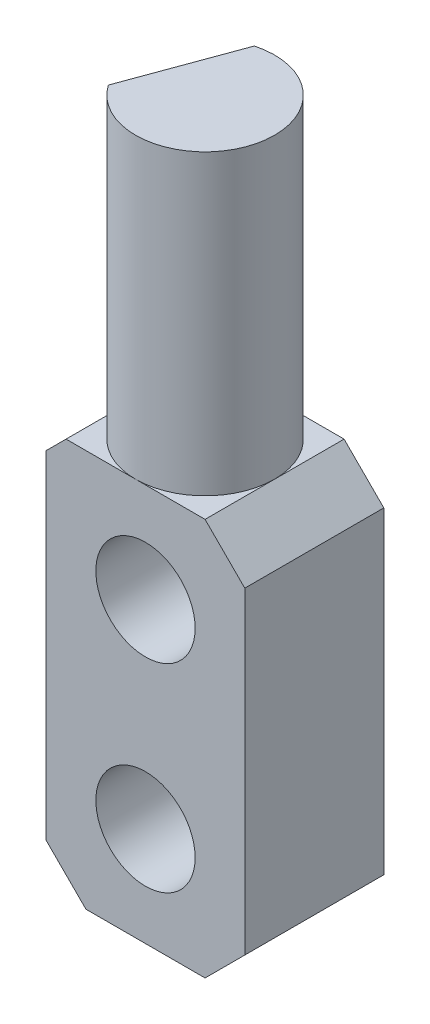
SolidWorks part; units mm, degrees
material "SUS304"
ref_plane "Front" through (0, 0, 0) normal (0, 0, 1) x (1, 0, 0)
ref_plane "Top" through (0, 0, 0) normal (0, 1, 0) x (1, 0, 0)
ref_plane "Right" through (0, 0, 0) normal (1, 0, 0) x (0, 0, -1)
sketch "Sketch1" plane through (0, 0, 0) normal (0, 0, 1) x (1, 0, 0)
  line L1 (0, 0) -> (10, 0)
  line L2 (0, 0) -> (0, 20)
  line L3 (0, 20) -> (10, 20)
  line L4 (10, 0) -> (10, 20)
  dimension "D1" = 20
  dimension "D2" = 10
extrude "Boss-Extrude1" add sketch "Sketch1" along normal blind 7
sketch "Sketch2" plane through (0, 20, 0) normal (0, 1, 0) x (1, 0, 0)
  line L0 (10, 0) -> (0, 0) construction
  line L1 (10, -7) -> (0, -7) construction
  line L2 (0, -7) -> (0, 0) construction
  circle A0 centre (4.5, -3.5) radius 3.5
  dimension "D1" = 4.5
extrude "Boss-Extrude2" add sketch "Sketch2" along normal blind 15
sketch "Sketch3" plane through (0, 0, 7) normal (0, 0, 1) x (1, 0, 0)
  line L0 (0, 20) -> (0, 0) construction
  line L1 (0, 0) -> (10, 0) construction
  circle A0 centre (5, 15) radius 2.5
  circle A1 centre (5, 5) radius 2.5
  dimension "D1" = 5
  dimension "D2" = 5
  dimension "D3" = 5
  dimension "D4" = 10
extrude "Cut-Extrude1" cut sketch "Sketch3" against normal through all
ref_plane "Plane1" through (-0.598, 0, 1.6314) normal (-0.3442, 0, 0.9389) x (0.9389, 0, 0.3442)
sketch "Sketch4" plane through (-0.598, 0, 1.6314) normal (-0.3442, 0, 0.9389) x (0.9389, 0, 0.3442)
  line L0 (1.9296, 35) -> (3.4196, 35)
  line L1 (8.9296, 35) -> (1.9296, 35) construction
  line L2 (3.4196, 35) -> (3.4196, 34.4)
  line L3 (3.4196, 34.4) -> (3.9196, 34.4)
  line L4 (3.9196, 34.4) -> (3.9196, 33.4)
  line L5 (3.9196, 33.4) -> (1.9296, 31.266)
  line L6 (1.9296, 35) -> (1.9296, 20) construction
  line L7 (1.9296, 31.266) -> (1.9296, 35)
  line L8 (5.4296, 35) -> (5.4296, 20) construction
  dimension "D1" = 0.5
  dimension "D2" = 1.51
  dimension "D3" = 0.6
  dimension "D4" = 1
  dimension "D5" = 43
extrude "Cut-Extrude2" cut sketch "Sketch4" along normal through all and the other way through all
chamfer "Chamfer1" distance 2 angle 45 3 edges at (0, 0, 3.5) (10, 0, 3.5) (10, 20, 3.5)
chamfer "Chamfer2" distance 1 angle 45 1 edges at (0, 20, 3.5)
